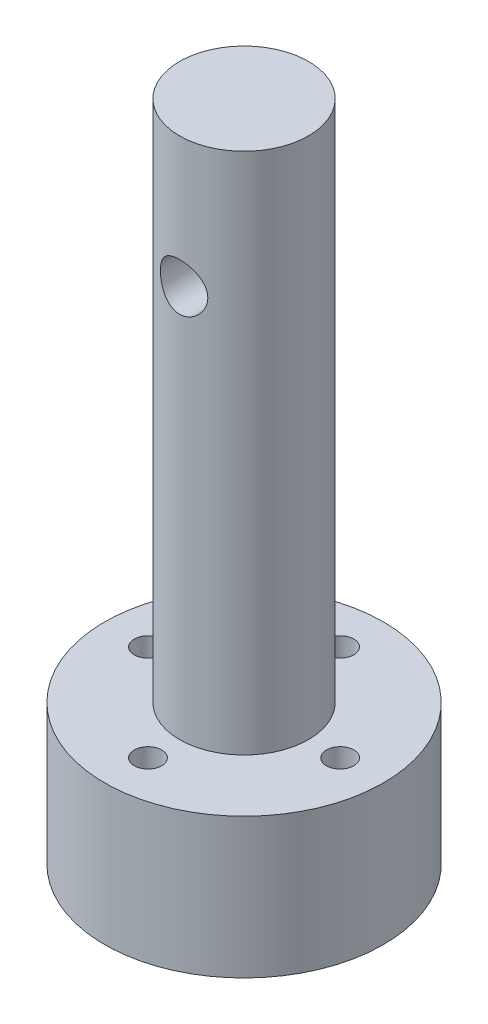
SolidWorks part; units mm, degrees
ref_plane "Front Plane" through (0, 0, 0) normal (0, 0, 1) x (1, 0, 0)
ref_plane "Top Plane" through (0, 0, 0) normal (0, 1, 0) x (1, 0, 0)
ref_plane "Right Plane" through (0, 0, 0) normal (1, 0, 0) x (0, 0, -1)
sketch "Sketch1" plane through (0, 0, 0) normal (0, 1, 0) x (1, 0, 0)
  circle A0 centre (0, 0) radius 10.16
  circle A1 centre (7, 0) radius 1
  circle A2 centre (0, -7) radius 1
  circle A3 centre (-7, 0) radius 1
  circle A4 centre (0, 7) radius 1
  point P14 (0, 0)
  dimension "D1" = 20.32
  dimension "D2" = 2
  dimension "D3" = 7
  dimension "D4" = 4
extrude "Boss-Extrude1" add sketch "Sketch1" along normal blind 19.05
sketch "Sketch2" plane through (0, 19.05, 0) normal (0, 1, 0) x (1, 0, 0)
  circle A0 centre (0, 0) radius 4.699
  dimension "D1" = 9.398
extrude "Boss-Extrude2" add sketch "Sketch2" along normal blind 38.1
sketch "Sketch3" plane through (0, 0, 0) normal (0, 1, 0) x (1, 0, 0)
  circle A0 centre (0, 0) radius 3.429
  dimension "D1" = 6.858
sketch "Sketch4" plane through (0, 0, 0) normal (0, -1, 0) x (1, 0, 0)
  circle A1 centre (0, 0) radius 10.16
  circle A2 centre (0, 0) radius 10.16
  dimension "D1" = 0
extrude "Cut-Extrude2" cut sketch "Sketch4" against normal blind 8.842
extrude "Cut-Extrude3" cut sketch "Sketch3" along normal blind 3.175 from surface starting at face at (7, 8.842, -1)
sketch "Sketch5" plane through (0, 0, 0) normal (0, 0, 1) x (1, 0, 0)
  line L0 (4.699, 57.15) -> (-4.699, 57.15) construction
  circle A0 centre (0, 47.625) radius 1.727
  dimension "D1" = 3.454
  dimension "D2" = 9.525
extrude "Cut-Extrude4" cut sketch "Sketch5" against normal through all both and the other way through all
equation "\"D3@Sketch1\"=7MM"
equation "\"D2@Sketch1\"=2MM"
equation "\"tightTol\"= 0.005in"
equation "\"normTol\"= 0.01in"
equation "\"looseTol\"= 0.02in"
equation "\"D1@Sketch2\"=0.375000-\"tightTol\""
equation "\"D1@Sketch3\"=1/4+\"looseTol\""
equation "\"D1@Cut-Extrude2\"= 15.7mm - 0.25 - \"looseTol\""
equation "\"D1@Sketch5\"=3.2mm+\"normTol\""
